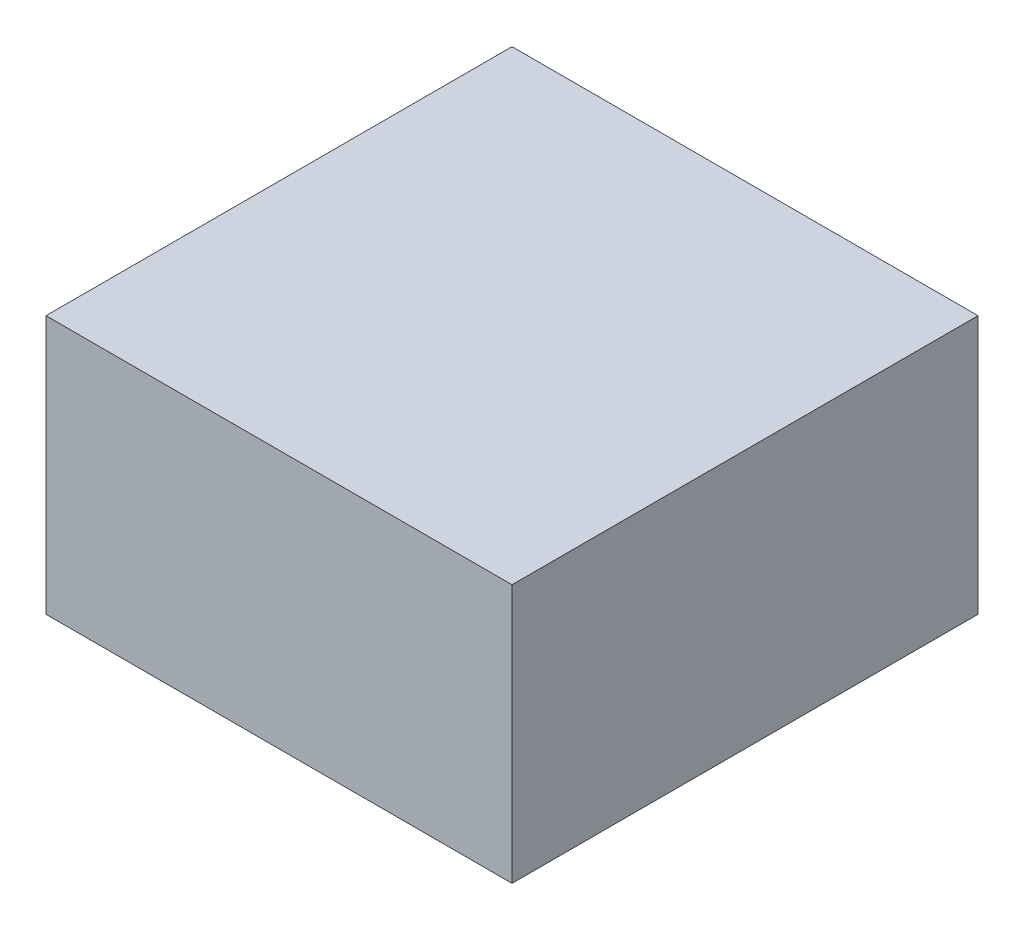
SolidWorks part; units mm, degrees
ref_plane "Front Plane" through (0, 0, 0) normal (0, 0, 1) x (1, 0, 0)
ref_plane "Top Plane" through (0, 0, 0) normal (0, 1, 0) x (1, 0, 0)
ref_plane "Right Plane" through (0, 0, 0) normal (1, 0, 0) x (0, 0, -1)
sketch "Sketch1" plane through (0, 0, 0) normal (0, 1, 0) x (1, 0, 0)
  line L1 (-273, -273) -> (273, -273)
  line L2 (-273, -273) -> (-273, 273)
  line L3 (-273, 273) -> (273, 273)
  line L4 (273, -273) -> (273, 273)
  line L5 (-273, -273) -> (273, 273) construction
  line L6 (-273, 273) -> (273, -273) construction
  line L7 (-270, -270) -> (270, -270)
  line L8 (-270, -270) -> (-270, 270)
  line L9 (-270, 270) -> (270, 270)
  line L10 (270, -270) -> (270, 270)
  line L11 (-270, -270) -> (270, 270) construction
  line L12 (-270, 270) -> (270, -270) construction
  point P0 (0, 0)
  point P7 (0, 0)
  dimension "D1" = 3
  dimension "D2" = 540
extrude "Boss-Extrude1" add sketch "Sketch1" along normal blind 300
sketch "Sketch2" plane through (0, 300, 0) normal (0, 1, 0) x (1, 0, 0)
  line L5 (-273, -273) -> (273, -273)
  line L6 (-273, -273) -> (-273, 273)
  line L7 (-273, 273) -> (273, 273)
  line L8 (273, -273) -> (273, 273)
  line L9 (-273, -273) -> (273, 273) construction
  line L10 (-273, 273) -> (273, -273) construction
  point P0 (0, 0)
  point P1 (0, 0)
extrude "Boss-Extrude2" add sketch "Sketch2" along normal blind 3
